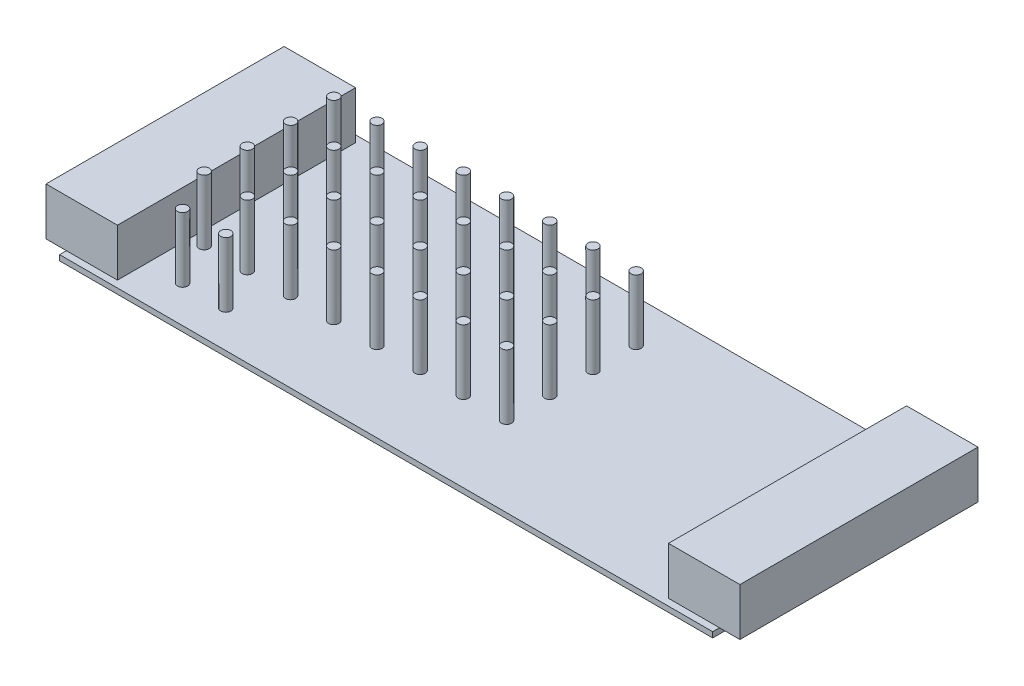
SolidWorks part; units mm, degrees
ref_plane "Front Plane" through (0, 0, 0) normal (0, 0, 1) x (1, 0, 0)
ref_plane "Top Plane" through (0, 0, 0) normal (0, 1, 0) x (1, 0, 0)
ref_plane "Right Plane" through (0, 0, 0) normal (1, 0, 0) x (0, 0, -1)
sketch "Sketch1" plane through (0, 0, 0) normal (0, 1, 0) x (1, 0, 0)
  line L1 (-96, -37) -> (96, -37)
  line L2 (-96, -37) -> (-96, 37)
  line L3 (-96, 37) -> (96, 37)
  line L4 (96, -37) -> (96, 37)
  line L5 (-96, -37) -> (96, 37) construction
  line L6 (-96, 37) -> (96, -37) construction
  point P0 (0, 0)
  dimension "D1" = 192
  dimension "D2" = 74
extrude "Boss-Extrude1" add sketch "Sketch1" along normal blind 1.6
sketch "Sketch2" plane through (0, 1.6, 0) normal (0, 1, 0) x (1, 0, 0)
  circle A0 centre (-77.0185, 24.6194) radius 1.5
  dimension "D1" = 3
extrude "Boss-Extrude2" add sketch "Sketch2" along normal blind 19 and the other way blind 7
pattern_linear "LPattern1" count 8 spacing 12.7 along (1, 0, 0) count 4 spacing 12.7 along (0, 0, 1) of "Boss-Extrude2"
sketch "Sketch3" plane through (0, 1.6, 0) normal (0, 1, 0) x (1, 0, 0)
  line L0 (-57.9524, -26.1806) -> (-70.6685, -26.1806) construction
  line L1 (-77.0185, -13.4806) -> (-64.3185, -13.4806) construction
  line L2 (-70.6685, -13.4806) -> (-70.6685, -26.1806) construction
  circle A0 centre (-70.6685, -26.1806) radius 1.5
  circle A1 centre (-57.9524, -26.1806) radius 1.5
  circle A2 centre (-77.0185, -13.4806) radius 1.5 construction
  circle A3 centre (-64.3185, -13.4806) radius 1.5 construction
  circle A4 centre (-77.0185, -13.4806) radius 1.5 construction
  circle A5 centre (-64.3185, -13.4806) radius 1.5 construction
  dimension "D1" = 3
  dimension "D2" = 12.7
extrude "Boss-Extrude3" add sketch "Sketch3" along normal up to surface and the other way up to surface up to face at (-77.0185, 20.6, 14.9806) other way up to face at (-77.0185, -5.4, 14.9806)
sketch "Sketch4" plane through (0, 1.6, 0) normal (0, 1, 0) x (1, 0, 0)
  line L0 (-96, 0) -> (-81, 0) construction
  line L1 (-81, 35) -> (-102, 35)
  line L2 (-81, 35) -> (-81, -35)
  line L3 (-81, -35) -> (-102, -35)
  line L4 (-102, 35) -> (-102, -35)
  line L5 (-96, 37) -> (-96, -37) construction
  line L6 (96, -37) -> (96, 37) construction
  line L7 (81, 35) -> (102, 35)
  line L8 (81, 35) -> (81, -35)
  line L9 (81, -35) -> (102, -35)
  line L10 (102, 35) -> (102, -35)
  dimension "D1" = 70
  dimension "D2" = 21
  dimension "D3" = 15
  dimension "D4" = 15
extrude "Boss-Extrude4" add sketch "Sketch4" along normal blind 14
